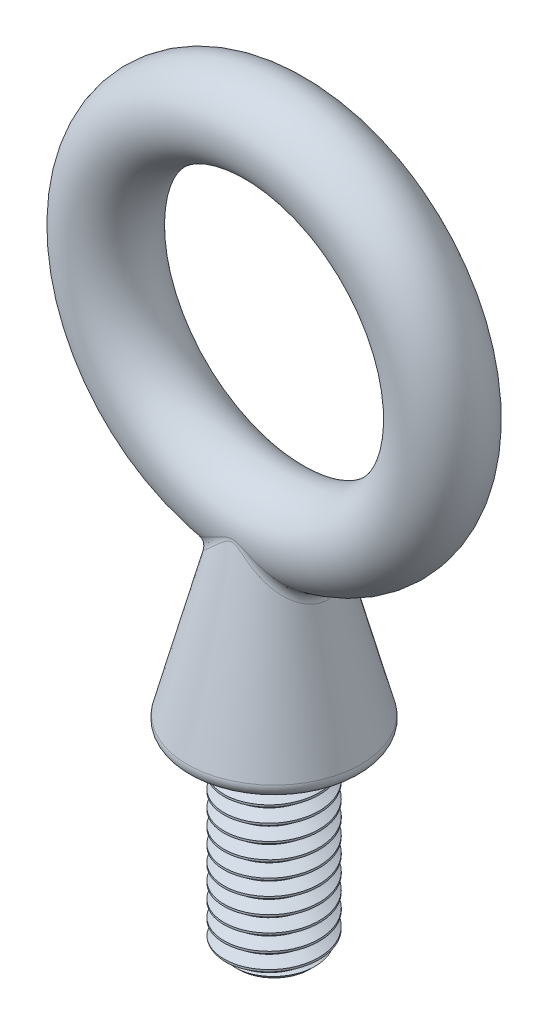
SolidWorks part; units mm, degrees
note: '?' marks a value the reader was unsure of.
ref_plane "Front Plane" through (0, 0, 0) normal (0, 0, 1) x (1, 0, 0)
ref_plane "Top Plane" through (0, 0, 0) normal (0, 1, 0) x (1, 0, 0)
ref_plane "Right Plane" through (0, 0, 0) normal (1, 0, 0) x (0, 0, -1)
sketch "Sketch1" plane through (0, 0, 0) normal (0, 0, 1) x (1, 0, 0)
  line L0 (0, -21.0344) -> (0, -54.3719) construction
  line L1 (-4.7625, -54.3719) -> (4.7625, -54.3719) construction
  line L2 (4.9344, -54.2727) -> (4.9344, -55.8602) construction
  line L3 (0, -21.0344) -> (0, -12.7) construction
  line L4 (-8.7312, -35.3219) -> (8.7313, -35.3219) construction
  line L5 (4.9344, -55.8602) -> (3.5595, -55.0664) construction
  line L6 (3.5595, -55.0664) -> (4.9344, -54.2727) construction
  line L7 (3.5595, -55.0664) -> (3.7314, -55.0664) construction
  line L8 (4.9344, -55.0664) -> (4.7625, -55.0664) construction
  line L9 (3.7314, -55.1656) -> (3.7314, -54.9672) construction
  line L10 (4.7625, -55.7609) -> (4.7625, -54.3719) construction
  line L11 (4.8484, -55.8105) -> (4.8484, -54.3223) construction
  circle A0 centre (0, 0) radius 21.0344 construction
  circle A1 centre (0, 16.8672) radius 4.1672 construction
  circle A2 centre (0, 0) radius 12.7 construction
  point P7 (0, -21.0344)
  point P9 (0, -35.3219)
  point P10 (0, 21.0344)
  point P11 (0, 12.7)
  point P14 (0, -54.3719)
  point P17 (0, 0)
  point P19 (0, -16.8672)
  point P21 (0, -35.3219)
  point P32 (3.7314, -55.0664)
  point P35 (4.7625, -55.0664)
  point P38 (4.8484, -55.0664)
  dimension "Pitch" = 1.5875
  dimension "D1" = 0.1984
sketch "Sketch2" plane through (0, 0, 0) normal (0, 1, 0) x (1, 0, 0)
  circle A0 centre (0, 0) radius 4.7625
extrude "Boss-Extrude1" add sketch "Sketch2" against normal up to vertex (54.3719 mm away) from vertex at -35.3219 starting at point (0, -35.3219, 0)
sketch "Sketch3" plane through (0, -54.3719, 0) normal (0, -1, 0) x (1, 0, 0)
  circle A1 centre (0, 0) radius 4.7625
  circle A2 centre (0, 0) radius 4.7625
  point P0 (4.7625, 0)
  point P1 (0, -4.7625)
  dimension "D1" = 0
sketch "Sketch4" plane through (0, 0, 0) normal (0, 0, 1) x (1, 0, 0)
  line L0 (3.7314, -54.9672) -> (3.7314, -55.1656)
  line L1 (3.7314, -55.1656) -> (4.8484, -55.8105)
  line L2 (4.8484, -55.8105) -> (4.8484, -54.3223)
  line L3 (4.8484, -54.3223) -> (3.7314, -54.9672)
sketch "Sketch5" plane through (0, -54.3719, 0) normal (0, -1, 0) x (1, 0, 0)
  circle A0 centre (0, 0) radius 3.5595
extrude "Cut-Extrude1" cut sketch "Sketch5" against normal through all draft 45 flip side to cut
sketch "Sketch6" plane through (0, 0, 0) normal (1, 0, 0) x (0, 0, -1)
  circle A0 centre (0, 16.8672) radius 4.1672
ref_axis "Axis1" through (0, 0, -7.6398) along (0, 0, 1)
revolve "Revolve1" add sketch "Sketch6" angle 360 about axis through (0, 0, -7.6398) along (0, 0, 1)
sketch "Sketch8" plane through (0, 0, 0) normal (0, 0, 1) x (1, 0, 0)
  line L0 (0, -35.3219) -> (0, -16.8672)
  line L1 (0, -16.8672) -> (-4.1672, -16.8672)
  line L2 (-7.6895, -35.3219) -> (-8.7312, -35.3219) construction
  line L3 (-8.7312, -35.3219) -> (-8.7312, -34.2801) construction
  line L4 (0, -35.3219) -> (8.7312, -35.3219) construction
  line L5 (-8.7312, -35.3219) -> (8.7313, -35.3219) construction
  line L6 (-8.6967, -34.014) -> (-4.1672, -16.8672)
  line L7 (-8.7312, -35.3219) -> (0, -35.3219) construction
  line L9 (-7.6895, -35.3219) -> (0, -35.3219)
  arc A0 (-8.6967, -34.014) -> (-7.6895, -35.3219) centre (-7.6895, -34.2801) ccw
  circle A1 centre (0, -16.8672) radius 4.1672 construction
  dimension "D1" = 1.0418
revolve "Revolve2" add sketch "Sketch8" angle 360 about L0
fillet "Fillet1" radius 1.0418 1 edges at (4.338, -19.8199, 2.3783)
sketch "SketchX" plane through (0, 0, 0) normal (1, 0, 0) x (0, 0, -1)
  line L0 (4.7625, -54.3719) -> (4.7625, -50.4031) construction
  line L1 (0, -54.3719) -> (4.7625, -54.3719) construction
  dimension "D1" = 3.9688
  dimension "D2" = 4.7625
ref_axis "Center Axis 1" through (0, 21.5506, 0) along (0, -1, 0)?
ref_axis "Center Axis 2" through (0, 0, -7.6398) along (0, 0, 1)?
curve "Helix/Spiral1" pitch 1.5875 height 20.6375 turns 13 parameters "Pitch"=1.5875
ref_plane "Plane1" through (0, -35.3219, 0) normal (0, -1, 0) x (1, 0, 0)
split "Split1" trim tools "Plane1" bodies to split 109 resulting bodies 110 111
sweep "Cut-Sweep1" cut profiles "Sketch4" path "Helix/Spiral1" align with end faces yes
sketch "Sketch9" plane through (0, -35.3219, 0) normal (0, -1, 0) x (1, 0, 0)
  line L0 (-8.7312, 0) -> (8.7313, 0) construction
  circle A0 centre (0, 0) radius 4.7625
extrude "Boss-Extrude2" add sketch "Sketch9" along normal blind 2.54 draft 45
equation "\"D3@Helix/Spiral1\" = \"Pitch@Helix/Spiral1\" + \"Thread Lg.@Sketch1\""
equation "\"D1@Sketch8\" = \"A@Sketch1\" / 8"
equation "\"D1@Fillet1\" = \"A@Sketch1\" / 8"
equation "\"D1@SketchX\"= \"Pitch@Helix/Spiral1\"*2.5"
equation "\"D1@Sketch1\"=\"Pitch@Sketch1\"/8"
equation "\"Pitch@Helix/Spiral1\"=\"Pitch@Sketch1\""
equation "\"D2@SketchX\" = \"Thread OD@Sketch1\" / 2"
